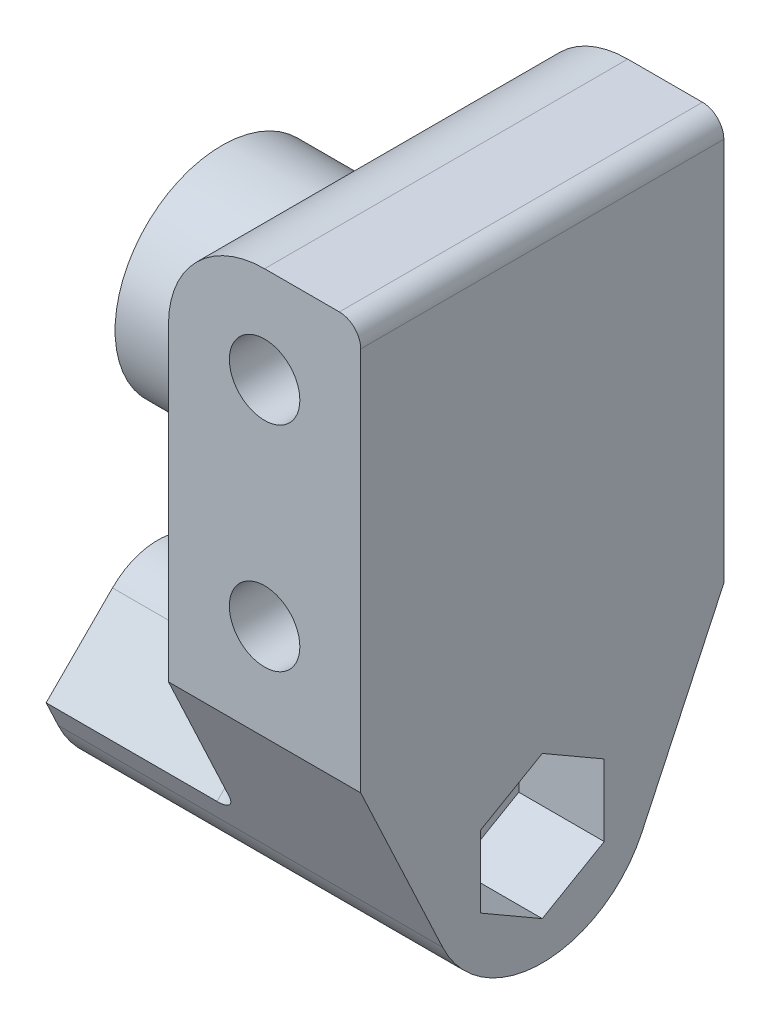
SolidWorks part; units mm, degrees
ref_plane "Front Plane" through (0, 0, 0) normal (0, 0, 1) x (1, 0, 0)
ref_plane "Top Plane" through (0, 0, 0) normal (0, 1, 0) x (1, 0, 0)
ref_plane "Right Plane" through (0, 0, 0) normal (1, 0, 0) x (0, 0, -1)
sketch "Sketch2" plane through (0, 0, 0) normal (0, 0, 1) x (1, 0, 0)
  line L0 (0, 0) -> (0, 10) construction
  line L1 (-4.5, 0) -> (-4.5, 10)
  line L2 (4.5, -4.5) -> (4.5, 14.5)
  line L3 (0, 14.5) -> (4.5, 14.5)
  line L4 (0, -4.5) -> (4.5, -4.5)
  arc A0 (-4.5, 0) -> (0, -4.5) centre (0, 0) ccw
  arc A1 (0, 14.5) -> (-4.5, 10) centre (0, 10) ccw
  circle A2 centre (0, 10) radius 1.65
  circle A3 centre (0, 0) radius 1.65
  point P3 (0, 5)
  dimension "D1" = 4.5
  dimension "D3" = 3.3
  dimension "D2" = 10
extrude "Boss-Extrude1" add sketch "Sketch2" along normal blind 17
sketch "Sketch3" plane through (4.5, 0, 0) normal (1, 0, 0) x (0, 0, -1)
  line L0 (-17, 5) -> (0, 5) construction
  line L1 (-17, -4.5) -> (-17, 14.5) construction
  line L2 (0, -4.5) -> (0, 14.5) construction
  line L3 (-8.5, 5) -> (-8.5, -10.5) construction
  line L4 (-13.1632, -12.6857) -> (-17, -4.5)
  line L5 (-17, -4.5) -> (0, -4.5)
  line L6 (0, -4.5) -> (-3.8368, -12.6857)
  circle A0 centre (-8.5, -10.5) radius 1.65
  arc A1 (-13.1632, -12.6857) -> (-3.8368, -12.6857) centre (-8.5, -10.5) ccw
  dimension "D2" = 3.3
  dimension "D3" = 3.5
  dimension "D1" = 15.5
extrude "Boss-Extrude2" add sketch "Sketch3" against normal up to vertex (9 mm away) up to point (-4.5, 0, 17)
sketch "Sketch4" plane through (0, -4.5, 0) normal (0, 1, 0) x (1, 0, 0)
  line L4 (0, -17) -> (0, 0)
  line L5 (0, 0) -> (-4.5, 0)
  line L6 (-4.5, 0) -> (-4.5, -17)
  line L7 (-4.5, -17) -> (0, -17)
  line L9 (0, 0) -> (-4.5, 0)
  line L10 (-4.5, 0) -> (-4.5, -17)
  line L11 (-4.5, -17) -> (0, -17)
  line L12 (0, -17) -> (0, 0)
  dimension "D1" = 0
extrude "Boss-Extrude4" add sketch "Sketch4" along normal up to surface (4.5 mm away) up to face at (-2.716, -2.716, 8.5)
sketch "Sketch8" plane through (-4.5, 0, 0) normal (-1, 0, 0) x (0, 0, 1)
  line L1 (8.5, -7.1514) -> (5.6, -8.8257)
  line L2 (5.6, -8.8257) -> (5.6, -12.1743)
  line L3 (5.6, -12.1743) -> (8.5, -13.8486)
  line L4 (8.5, -13.8486) -> (11.4, -12.1743)
  line L5 (11.4, -12.1743) -> (11.4, -8.8257)
  line L6 (11.4, -8.8257) -> (8.5, -7.1514)
  circle A0 centre (8.5, -10.5) radius 2.9 construction
  dimension "D1" = 5.8
extrude "Cut-Extrude2" cut sketch "Sketch8" against normal blind 13 from offset 5 offset against normal yes
sketch "Sketch11" plane through (-4.5, 0, 0) normal (1, 0, 0) x (0, 0, -1)
  line L0 (-17, 5) -> (0, 5) construction
  line L3 (-17, 10) -> (0, 10) construction
  line L4 (0, -4.5) -> (0, 14.5) construction
  line L5 (-17, -4.5) -> (-17, 14.5) construction
  circle A0 centre (-8.5, 5) radius 5
  dimension "D1" = 10
  dimension "D2" = 5
extrude "Boss-Extrude5" add sketch "Sketch11" against normal blind 6
fillet "Fillet1" radius 1 1 edges at (-4.5, 5, 3.5)
fillet "Fillet2" radius 1 1 edges at (4.5, 14.5, 8.5)
sketch "Sketch12" plane through (-4.5, 0, 0) normal (-1, 0, 0) x (0, 0, 1)
  line L3 (13.1632, -12.6857) -> (13.7265, -11.4839)
  line L4 (17, -4.5) -> (13.1632, -12.6857) construction
  line L5 (13.7265, -11.4839) -> (10.6213, -8.3787)
  line L6 (6.3787, -8.3787) -> (3.2735, -11.4839)
  line L7 (3.8368, -12.6857) -> (0, -4.5) construction
  line L8 (3.2735, -11.4839) -> (3.8368, -12.6857)
  line L9 (8.5, -10.5) -> (8.5, -7.5) construction
  arc A0 (10.6213, -8.3787) -> (6.3787, -8.3787) centre (8.5, -10.5) ccw
  arc A1 (3.8368, -12.6857) -> (13.1632, -12.6857) centre (8.5, -10.5) ccw construction
  arc A2 (3.8368, -12.6857) -> (13.1632, -12.6857) centre (8.5, -10.5) ccw
  circle A3 centre (8.5, -10.5) radius 1.65 construction
  circle A4 centre (8.5, -10.5) radius 1.65
  point P2 (0, 0)
  dimension "D1" = 6
extrude "Boss-Extrude6" add sketch "Sketch12" along normal blind 9
fillet "Fillet3" radius 1 3 edges at (-4.5, -9.9313, 12.1739) (-4.5, -9.9313, 4.8261) (-4.5, -7.5, 8.5)
